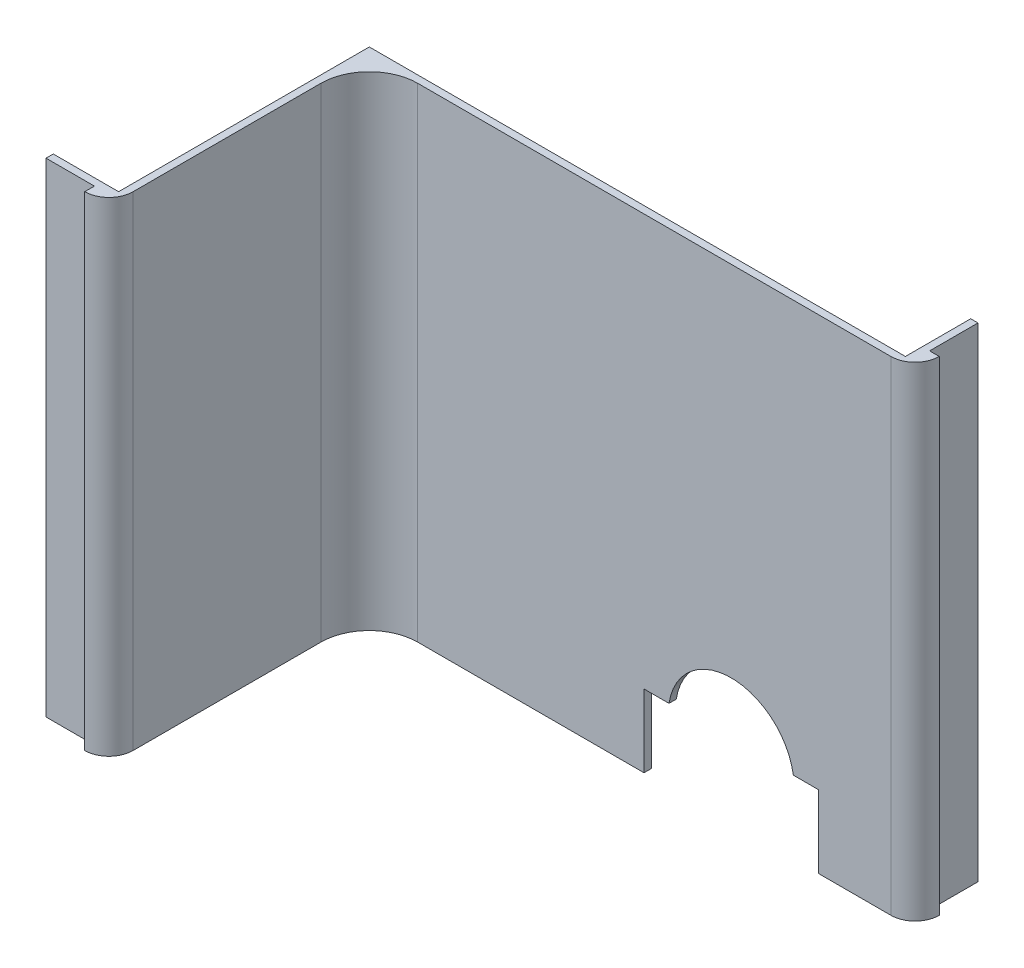
SolidWorks part; units mm, degrees
material "ABS"
ref_plane "Спереди" through (0, 0, 0) normal (0, 0, 1) x (1, 0, 0)
ref_plane "Сверху" through (0, 0, 0) normal (0, 1, 0) x (1, 0, 0)
ref_plane "Справа" through (0, 0, 0) normal (1, 0, 0) x (0, 0, -1)
sketch "Эскиз1" plane through (0, 0, 0) normal (0, 1, 0) x (1, 0, 0)
  line L0 (0, 0) -> (-97.768, 0)
  line L1 (-107.768, -10) -> (-107.768, -48.8)
  line L2 (-112.768, -53.8) -> (-112.768, -51.8)
  line L3 (-112.768, -51.8) -> (-122.768, -51.8)
  line L4 (5, 5) -> (3, 5)
  line L5 (3, 5) -> (3, 15)
  line L6 (3, 15) -> (1.5, 15)
  line L7 (0, 0) -> (0, 1.5) construction
  line L8 (1.5, 15) -> (1.5, 1.5)
  line L9 (-107.768, -48.8) -> (-109.268, -48.8) construction
  line L10 (-122.768, -51.8) -> (-122.768, -50.3)
  line L11 (-122.768, -50.3) -> (-109.268, -50.3)
  line L12 (-109.268, -50.3) -> (-109.268, 1.5)
  line L13 (-109.268, 1.5) -> (1.5, 1.5)
  arc A0 (-97.768, 0) -> (-107.768, -10) centre (-97.768, -10) ccw
  arc A1 (-107.768, -48.8) -> (-112.768, -53.8) centre (-112.768, -48.8) cw
  arc A2 (0, 0) -> (5, 5) centre (0, 5) ccw
  dimension "D1" = 97.768
  dimension "D2" = 5
  dimension "D6" = 10
  dimension "D9" = 5
  dimension "D3" = 2
  dimension "D4" = 1.5
  dimension "D5" = 1.5
  dimension "D7" = 1.5
  dimension "D8" = 38.8
  dimension "D10" = 2
  dimension "D11" = 1.5
  dimension "D12" = 10
  dimension "D13" = 10
extrude "Бобышка-Вытянуть1" add sketch "Эскиз1" along normal blind 100
sketch "Эскиз4" plane through (0, 0, 0) normal (0, 0, 1) x (1, 0, 0)
  line L0 (5, 0) -> (-15, 0) construction
  line L1 (-15, 0) -> (-51, 0)
  line L2 (-97.768, 0) -> (0, 0) construction
  line L3 (-51, 0) -> (-51, 15)
  line L4 (-51, 15) -> (-51, 13) construction
  line L5 (-51, 15) -> (-45.8452, 15)
  line L6 (-15, 0) -> (-15, 14.9972)
  line L7 (-15, 14.9972) -> (-20.1543, 14.9972)
  line L8 (-51, 13) -> (-15, 13) construction
  arc A0 (-45.8452, 15) -> (-20.1543, 14.9972) centre (-33, 13) cw
  point P16 (-45.8452, 15)
  point P17 (-20.1543, 14.9972)
  dimension "D4" = 13
  dimension "D1" = 20
  dimension "D2" = 36
  dimension "D3" = 15
  dimension "D5" = 2
  dimension "D6" = 14.9972
extrude "Вырез-Вытянуть1" cut sketch "Эскиз4" against normal through all
